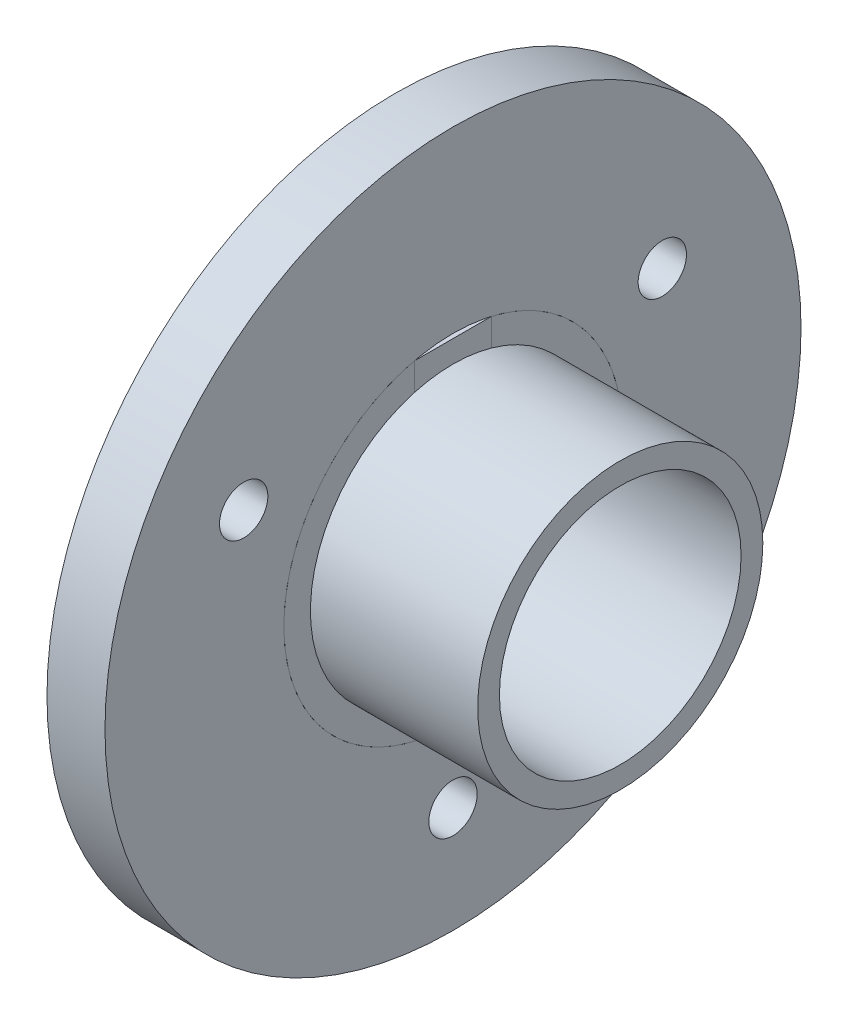
SolidWorks part; units mm, degrees
ref_plane "Спереди" through (0, 0, 0) normal (0, 0, 1) x (1, 0, 0)
ref_plane "Сверху" through (0, 0, 0) normal (0, 1, 0) x (1, 0, 0)
ref_plane "Справа" through (0, 0, 0) normal (1, 0, 0) x (0, 0, -1)
sketch "Эскиз1" plane through (0, 0, 0) normal (0, 0, 1) x (1, 0, 0)
  line L1 (-122.6026, -155.8076) -> (-148.6125, -155.8076) construction
  line L2 (-133.35, -155.8076) -> (-125.05, -155.8076) construction
  line L3 (-133.35, -141.0576) -> (-133.35, -170.5576) construction
  line L4 (-133.35, -141.0576) -> (-133.35, -170.5576) construction
  line L5 (-125.05, -170.5576) -> (-125.05, -141.0576) construction
  line L6 (-125.05, -170.5576) -> (-125.05, -141.0576) construction
  line L7 (-114.55, -143.3076) -> (-114.55, -168.3076) construction
  line L8 (-114.55, -143.3076) -> (-114.55, -168.3076) construction
  line L9 (-116.05, -138.3076) -> (-116.05, -173.3076) construction
  line L10 (-116.05, -138.3076) -> (-116.05, -173.3076) construction
  line L11 (-116.05, -143.3076) -> (-149.35, -143.3076)
  line L12 (-149.35, -143.3076) -> (-149.35, -138.3076)
  line L13 (-149.35, -138.3076) -> (-133.35, -138.3076)
  line L14 (-133.35, -138.3076) -> (-133.35, -141.0576)
  line L15 (-133.35, -141.0576) -> (-116.05, -141.0576)
  line L16 (-116.05, -141.0576) -> (-116.05, -143.3076)
  dimension "D1" = 5
  dimension "D2" = 16
revolve "Повернуть1" add sketch "Эскиз1" angle 360 about L1
ref_plane "Плоскость1" through (-133.35, 0, 0) normal (-1, 0, 0) x (0, 0, 1)
sketch "Эскиз2" plane through (-133.35, 0, 0) normal (-1, 0, 0) x (0, 0, 1)
  circle A0 centre (0, -155.8076) radius 17.5 construction
  circle A1 centre (0, -155.8076) radius 17.5
  circle A2 centre (0, -155.8076) radius 36
  arc A3 (31.1769, -148.8076) -> (21.6506, -132.3076) centre (21.6506, -143.3076) ccw construction
  circle A6 centre (-21.6506, -143.3076) radius 2.5
  circle A7 centre (-21.6506, -143.3076) radius 2.5
  circle A9 centre (0, -180.8076) radius 2.5
  circle A10 centre (0, -180.8076) radius 2.5
  circle A12 centre (21.6506, -143.3076) radius 2.5
  circle A13 centre (21.6506, -143.3076) radius 2.5
  dimension "D1" = 2
  dimension "D2" = 2
  dimension "D3" = 2
base flange "Базовая кромка1" sketch "Эскиз2" thickness 6 reverse thickness direction yes parameters "D1"=0.7366
sketch "Эскиз8" plane through (-149.35, 0, 0) normal (-1, 0, 0) x (0, 0, 1)
  line L0 (-4, -138.7708) -> (-4, -147.3076)
  line L1 (-4, -147.3076) -> (4, -147.3076)
  line L2 (4, -147.3076) -> (4, -138.7708)
  arc A0 (-4, -138.7708) -> (4, -138.7708) centre (0, -155.8076) cw
  circle A1 centre (0, -155.8076) radius 17.5 construction
  circle A5 centre (0, -155.8076) radius 12.5 construction
  point P7 (0, -147.3076)
  dimension "D1" = 8
  dimension "D2" = 4
extrude "Вырез-Вытянуть1" cut sketch "Эскиз8" against normal up to surface (16 mm away) up to face at (-133.35, -155.8076, -17.5)
sketch "Эскиз9" plane through (-149.35, 0, 0) normal (-1, 0, 0) x (0, 0, 1)
  line L0 (-4, -138.7708) -> (-4, -143.9649) construction
  line L1 (4, -138.7708) -> (-4, -138.7708)
  line L2 (4, -138.7708) -> (4, -147.3076)
  line L3 (4, -147.3076) -> (-4, -147.3076)
  line L4 (-4, -138.7708) -> (-4, -147.3076)
  arc A1 (-4, -143.9649) -> (4, -143.9649) centre (0, -155.8076) ccw construction
  dimension "D1" = 4
extrude "Бобышка-Вытянуть1" add sketch "Эскиз9" against normal up to surface (16 mm away) separate body up to face at (-133.35, -155.8076, 36)
sketch "Сгиб-Линии1" [suppressed] plane through (0, 0, 0) normal (0, 1, 0) x (1, 0, 0)
sketch "Граничная рамка1" [suppressed] plane through (0, 0, 0) normal (0, 1, 0) x (1, 0, 0)
sheet metal parameters "Листовой металл4" thickness 6 parameters "D1"=0.7366
flat pattern "Развертка4" [suppressed]
sketch "Сгиб-Линии2" plane through (0, 0, 0) normal (0, 1, 0) x (1, 0, 0)
sketch3d "Граничная рамка2" [suppressed]
  line L0 (35.9959, -36.004, 0) -> (-36.0041, -35.9959, 0) construction
  line L1 (36.0041, 35.9959, 0) -> (-35.9959, 36.004, 0) construction
  line L2 (35.9959, -36.004, 0) -> (36.0041, 35.9959, 0) construction
  line L3 (-36.0041, -35.9959, 0) -> (-35.9959, 36.004, 0) construction
